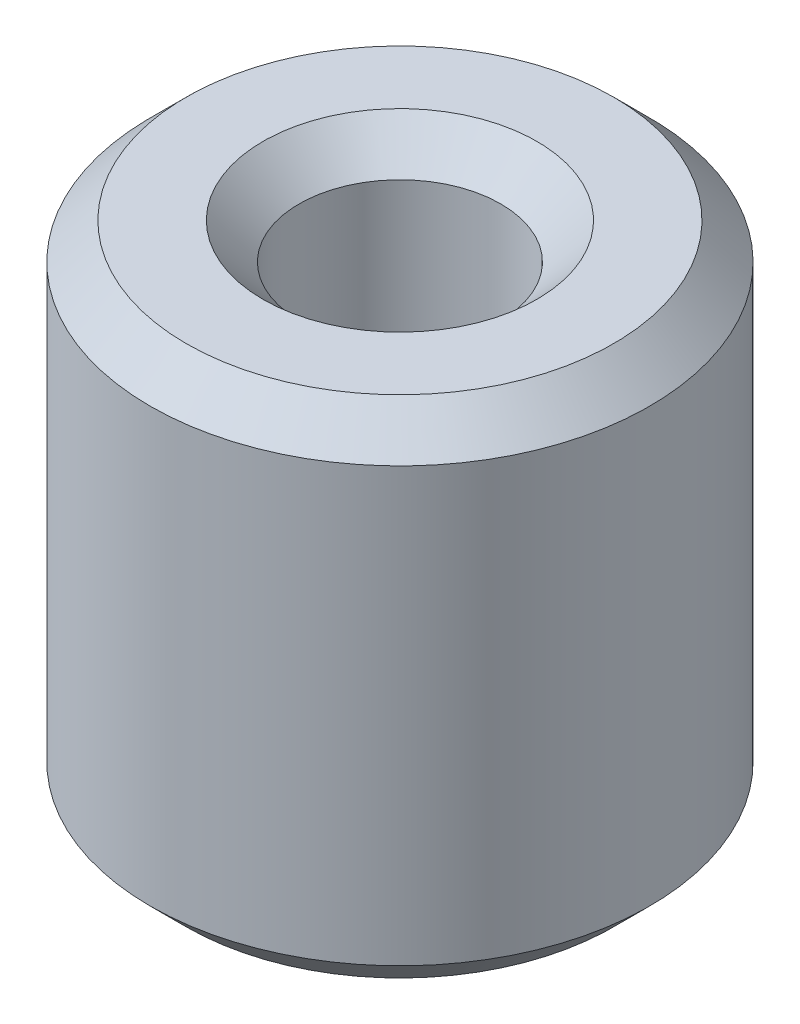
SolidWorks part; units mm, degrees
ref_plane "Front Plane" through (0, 0, 0) normal (0, 0, 1) x (1, 0, 0)
ref_plane "Top Plane" through (0, 0, 0) normal (0, 1, 0) x (1, 0, 0)
ref_plane "Right Plane" through (0, 0, 0) normal (1, 0, 0) x (0, 0, -1)
sketch "Sketch1" plane through (0, 0, 0) normal (0, 1, 0) x (1, 0, 0)
  circle A0 centre (0, 0) radius 27.5
  dimension "SLEEVE_OD" = 55
extrude "Boss-Extrude1" add sketch "Sketch1" along normal blind 55.6292
sketch "Sketch2" plane through (0, 0, 0) normal (0, 1, 0) x (1, 0, 0)
  circle A0 centre (0, 0) radius 11.1034
  dimension "BORE_D" = 22.2067
extrude "Cut-Extrude1" cut sketch "Sketch2" along normal through all
chamfer "Chamfer1" distance 3.9755 angle 45 4 edges at (0, 55.6292, 11.1034) (0, 0, 11.1034) (0, 0, 27.5) (0, 55.6292, 27.5)
